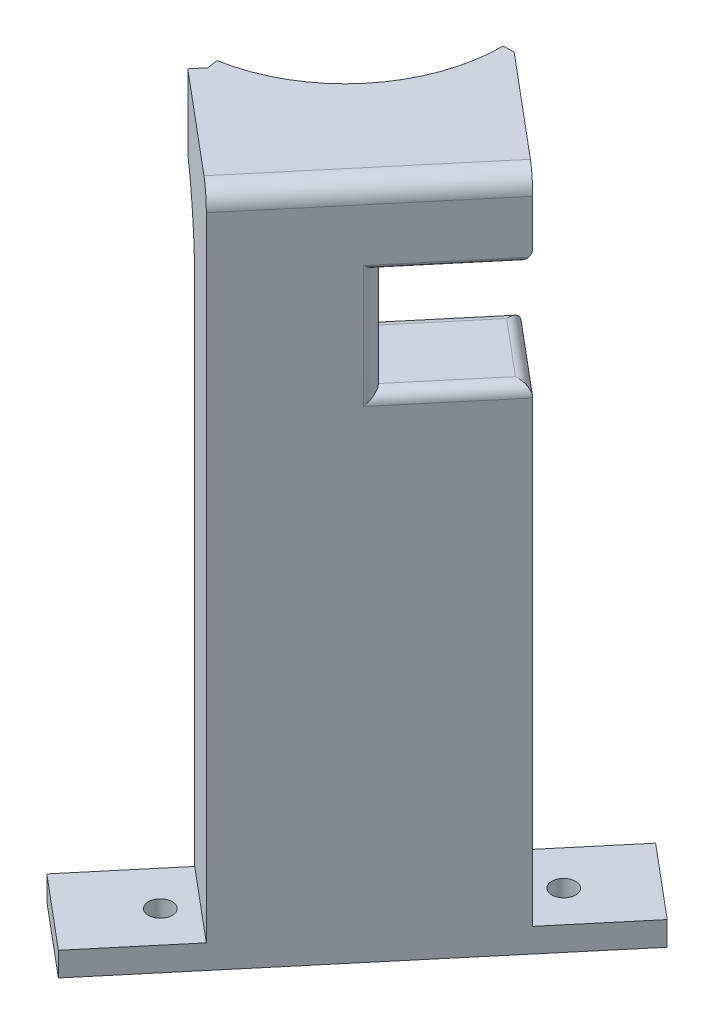
SolidWorks part; units mm, degrees
other "Markup1"
sketch "Sketch16" plane through (-5.2094, 14, 0) normal (0.4128, 0.8393, 0.3538) x (0.5563, 0.0753, -0.8276)
ref_plane "Front Plane" through (0, 0, 0) normal (0, 0, 1) x (1, 0, 0)
ref_plane "Top Plane" through (0, 0, 0) normal (0, 1, 0) x (1, 0, 0)
ref_plane "Right Plane" through (0, 0, 0) normal (1, 0, 0) x (0, 0, -1)
sketch "Sketch1" plane through (0, 0, 0) normal (0, 1, 0) x (1, 0, 0)
  line L0 (0, 0) -> (-45, 0)
  line L1 (0, 0) -> (-7.8142, 44.3163)
  circle A0 centre (0, 0) radius 42.1
  circle A1 centre (0, 0) radius 45
  circle A2 centre (0, 0) radius 30
  dimension "D1" = 84.2
  dimension "D2" = 90
  dimension "D3" = 60
  dimension "D4" = 80
extrude "Boss-Extrude1" add sketch "Sketch1" along normal blind 4 contours A2 L1 A0 L0 | L1 A1 L0 A0 region at (-25.6654, 0, -21.5358) region at (-43.55, 0, -0.5818)
extrude "Boss-Extrude2" add sketch "Sketch1<3>" along normal blind 14 contours L1 A1 L0 A0 region at (-43.55, 0, -0.5818)
sketch "Sketch1<3>" plane through (0, 0, 0) normal (0, 1, 0) x (1, 0, 0) same geometry as "Sketch1"
ref_plane "Plane1" through (0, -2.54, 0) normal (0, -1, 0) x (-1, 0, 0)
ref_plane "Plane2" through (0, -106.04, 0) normal (0, -1, 0) x (-1, 0, 0)
sketch "Sketch2" plane through (0, -106.04, 0) normal (0, -1, 0) x (-1, 0, 0)
  line L2 (7.8142, 44.3163) -> (5.2094, 29.5442)
  line L3 (30, 0) -> (45, 0)
  line L4 (7.8142, 44.3163) -> (5.2094, 29.5442)
  line L5 (30, 0) -> (45, 0)
  arc A2 (45, 0) -> (7.8142, 44.3163) centre (0, 0) ccw
  arc A3 (30, 0) -> (5.2094, 29.5442) centre (0, 0) ccw
  arc A4 (45, 0) -> (7.8142, 44.3163) centre (0, 0) ccw
  arc A5 (30, 0) -> (5.2094, 29.5442) centre (0, 0) ccw
  dimension "D1" = 0
sketch "Sketch3" plane through (0, 0, 0) normal (0, -1, 0) x (1, 0, 0)
  line L0 (-7.8142, -44.3163) -> (-45, 0)
  line L1 (-45, 0) -> (-75.6418, -25.7115)
  line L2 (-75.6418, -25.7115) -> (-38.4559, -70.0279)
  line L3 (-38.4559, -70.0279) -> (-7.8142, -44.3163)
  dimension "D1" = 40
extrude "Boss-Extrude3" add sketch "Sketch3" against normal up to surface (4 mm away) contours L3 L0 L1 L2 up to face at (-24.3855, 4, -20.4618)
sketch "Sketch4" plane through (0, 0, 0) normal (0, -1, 0) x (1, 0, 0)
  line L0 (-38.4559, -70.0279) -> (-19.3048, -53.9582)
  line L1 (-38.4559, -70.0279) -> (-7.8142, -44.3163) construction
  line L2 (-19.3048, -53.9582) -> (-56.4907, -9.6418)
  line L3 (-45, 0) -> (-75.6418, -25.7115) construction
  line L4 (-56.4907, -9.6418) -> (-75.6418, -25.7115)
  line L5 (-75.6418, -25.7115) -> (-38.4559, -70.0279)
  dimension "D1" = 25
extrude "Boss-Extrude4" add sketch "Sketch4" along normal blind 103.5
fillet "Fillet1" radius 20 1 edges at (-37.8978, 0, -31.8)
sketch "Sketch14" plane through (0, 4, 0) normal (0, 1, 0) x (1, 0, 0)
  line L0 (-7.8142, 44.3163) -> (-38.4559, 70.0279) construction
  line L1 (-38.4559, 70.0279) -> (-75.6418, 25.7115) construction
  line L2 (-75.6418, 25.7115) -> (-45, 0) construction
  line L9 (-7.3106, 41.4604) -> (-7.8142, 44.3163) construction
  line L10 (-45, 0) -> (-42.1, 0) construction
  line L12 (-7.8142, 44.3163) -> (-38.4559, 70.0279)
  line L13 (-38.4559, 70.0279) -> (-75.6418, 25.7115)
  line L14 (-75.6418, 25.7115) -> (-45, 0)
  line L15 (-7.3106, 41.4604) -> (-7.8142, 44.3163)
  line L16 (-45, 0) -> (-42.1, 0)
  arc A0 (-7.8142, 44.3163) -> (-45, 0) centre (0, 0) ccw construction
  arc A4 (-7.8142, 44.3163) -> (-45, 0) centre (0, 0) ccw construction
  arc A5 (-7.3106, 41.4604) -> (-42.1, 0) centre (0, 0) ccw construction
  arc A6 (-7.8142, 44.3163) -> (-45, 0) centre (0, 0) ccw
  arc A7 (-7.8142, 44.3163) -> (-45, 0) centre (0, 0) ccw
  arc A8 (-7.3106, 41.4604) -> (-42.1, 0) centre (0, 0) ccw
  arc M5 (-45, 0) -> (-7.8142, 44.3163) centre (0, 0) cw
  line M6 (-7.8142, 44.3163) -> (-38.4559, 70.0279)
  line M7 (-38.4559, 70.0279) -> (-75.6418, 25.7115)
  line M8 (-75.6418, 25.7115) -> (-45, 0)
extrude "Boss-Extrude7" add sketch "Sketch14" along normal blind 15 contours M8 M5 M6 M7 | A8 L15 L16 M5 region at (-44.3759, 4, -37.2358) region at (-8.1353, 4, -42.7874)
fillet "Fillet2" radius 5 1 edges at (-57.0489, 19, -47.8697)
sketch "Sketch6" plane through (18.5929, 0, -22.1582) normal (0.6428, 0, -0.766) x (-0.766, 0, -0.6428)
  line L0 (74.472, 14) -> (74.472, -103.5) construction
  line L1 (49.472, -103.5) -> (74.472, -103.5)
  line L2 (49.472, -103.5) -> (49.472, -97.5)
  line L3 (49.472, -97.5) -> (74.472, -97.5)
  line L4 (74.472, -103.5) -> (74.472, -97.5)
  dimension "D1" = 6
extrude "Boss-Extrude5" add sketch "Sketch6" along normal blind 25.4
sketch "Sketch7" plane through (-18.5929, 0, 22.1582) normal (-0.6428, 0, 0.766) x (0.766, 0, 0.6428)
  line L4 (-49.472, -103.5) -> (-49.472, -97.5)
  line L5 (-74.472, -103.5) -> (-49.472, -103.5)
  line L6 (-74.472, -97.5) -> (-74.472, -103.5)
  line L7 (-49.472, -97.5) -> (-74.472, -97.5)
  line L8 (-49.472, -103.5) -> (-49.472, -97.5)
  line L9 (-74.472, -103.5) -> (-49.472, -103.5)
  line L10 (-74.472, -97.5) -> (-74.472, -103.5)
  line L11 (-49.472, -97.5) -> (-74.472, -97.5)
  dimension "D1" = 0
extrude "Boss-Extrude6" add sketch "Sketch7" along normal blind 31.75
sketch "Sketch8" plane through (0, -97.5, 0) normal (0, 1, 0) x (1, 0, 0)
  circle A1 centre (-24.9091, 67.6646) radius 2.5527
  circle A2 centre (-24.9091, 67.6646) radius 2.5527
  circle A3 centre (-73.8895, 9.292) radius 2.5527
  circle A4 centre (-73.8895, 9.292) radius 2.5527
  dimension "D1" = 0
  dimension "D2" = 0
extrude "Cut-Extrude1" cut sketch "Sketch8" against normal blind 25.4 contours A4 | A2 region at (-73.8895, -97.5, -9.292)
sketch "Sketch9" plane through (0, -103.5, 0) normal (0, -1, 0) x (1, 0, 0)
  circle A0 centre (-73.8895, -9.292) radius 3.175
  circle A1 centre (-24.9091, -67.6646) radius 3.175
  dimension "D1" = 6.35
  dimension "D2" = 6.35
extrude "Cut-Extrude2" cut sketch "Sketch9" against normal blind 25.4
sketch "Sketch10" plane through (0, -97.5, 0) normal (0, 1, 0) x (1, 0, 0)
  line L1 (-76.8992, -14.6801) -> (-22.1291, -14.6801)
  line L2 (-76.8992, -14.6801) -> (-76.8992, 89.4854)
  line L3 (-76.8992, 89.4854) -> (-22.1291, 89.4854)
  line L4 (-22.1291, -14.6801) -> (-22.1291, 89.4854)
  line L5 (-144.4229, -81.7018) -> (69.164, -81.7018)
  line L6 (-144.4229, -81.7018) -> (-144.4229, 136.0266)
  line L7 (-144.4229, 136.0266) -> (69.164, 136.0266)
  line L8 (69.164, -81.7018) -> (69.164, 136.0266)
  line M11 (-75.6418, 25.7115) -> (-96.0503, 1.3896)
  line M12 (-96.0503, 1.3896) -> (-76.8992, -14.6801)
extrude "Cut-Extrude3" [suppressed] cut sketch "Sketch10" along normal blind 132.4 contours L5 L8 L7 L6 L4 L1 L2 L3 M12 M11 | L2 L1 L4 L3
ref_plane "Plane3" through (-64.7093, 0, -54.2976) normal (-0.766, 0, -0.6428) x (-0.6428, 0, 0.766)
sketch "Sketch18" plane through (0, -103.5, 0) normal (0, -1, 0) x (1, 0, 0)
  line L4 (-96.0503, -1.3896) -> (-22.1291, -89.4854)
  line L5 (-22.1291, -89.4854) -> (-2.978, -73.4157)
  line L6 (-2.978, -73.4157) -> (-76.8992, 14.6801)
  line L7 (-76.8992, 14.6801) -> (-96.0503, -1.3896)
  line L8 (-96.0503, -1.3896) -> (-22.1291, -89.4854)
  line L9 (-22.1291, -89.4854) -> (-2.978, -73.4157)
  line L10 (-2.978, -73.4157) -> (-76.8992, 14.6801)
  line L11 (-76.8992, 14.6801) -> (-96.0503, -1.3896)
  circle A1 centre (-24.9091, -67.6646) radius 3.175
  circle A2 centre (-24.9091, -67.6646) radius 3.175
  circle A3 centre (-73.8895, -9.292) radius 3.175
  circle A4 centre (-73.8895, -9.292) radius 3.175
  dimension "D1" = 0
  dimension "D2" = 0
  dimension "D3" = 0
extrude "Boss-Extrude9" add sketch "Sketch18" along normal blind 57.15
sketch "Sketch19" plane through (0, -97.5, 0) normal (0, 1, 0) x (1, 0, 0)
  line L0 (-56.4907, 9.6418) -> (-75.6418, 25.7115) construction
  line L1 (-75.6418, 25.7115) -> (-96.0503, 1.3896) construction
  line L2 (-96.0503, 1.3896) -> (-76.8992, -14.6801) construction
  line L3 (-76.8992, -14.6801) -> (-56.4907, 9.6418) construction
  line L4 (-38.4559, 70.0279) -> (-19.3048, 53.9582) construction
  line L5 (-19.3048, 53.9582) -> (-2.978, 73.4157) construction
  line L6 (-2.978, 73.4157) -> (-22.1291, 89.4854) construction
  line L7 (-22.1291, 89.4854) -> (-38.4559, 70.0279) construction
  line L8 (-56.4907, 9.6418) -> (-75.6418, 25.7115)
  line L9 (-75.6418, 25.7115) -> (-96.0503, 1.3896)
  line L10 (-96.0503, 1.3896) -> (-76.8992, -14.6801)
  line L11 (-76.8992, -14.6801) -> (-56.4907, 9.6418)
  line L12 (-38.4559, 70.0279) -> (-19.3048, 53.9582)
  line L13 (-19.3048, 53.9582) -> (-2.978, 73.4157)
  line L14 (-2.978, 73.4157) -> (-22.1291, 89.4854)
  line L15 (-22.1291, 89.4854) -> (-38.4559, 70.0279)
  circle A0 centre (-73.8895, 9.292) radius 3.175 construction
  circle A1 centre (-24.9091, 67.6646) radius 3.175 construction
  circle A2 centre (-73.8895, 9.292) radius 3.175
  circle A3 centre (-24.9091, 67.6646) radius 3.175
extrude "Cut-Extrude6" cut sketch "Sketch19" against normal blind 34.925
mirror "Mirror2" about plane through (-64.7093, 0, -54.2976) normal (-0.766, 0, -0.6428) of bodies 115 108
sketch "Sketch11" plane through (0, 19, 0) normal (0, 1, 0) x (1, 0, 0)
  line L0 (-67.6166, -74.3731) -> (52.0413, 76.7386)
  line L1 (52.0413, 76.7386) -> (-7.7876, 112.2458)
  line L2 (-7.7876, 112.2458) -> (-112.5342, -8.8462)
  line L3 (-112.5342, -8.8462) -> (-67.6166, -74.3731)
extrude "Cut-Extrude4" cut sketch "Sketch11" against normal through all both and the other way through all
sketch "Sketch13" plane through (-72.3698, 0, -60.7254) normal (0.766, 0, 0.6428) x (0.6428, 0, -0.766)
  line L0 (28.9254, 14) -> (28.9254, -132.425) construction
  line L1 (28.9254, -1) -> (0, -1)
  line L2 (28.9254, -1) -> (28.9254, -29.5)
  line L3 (28.9254, -29.5) -> (0, -29.5)
  line L4 (0, -1) -> (0, -29.5)
  line L6 (-28.9254, -103.5) -> (28.9254, -103.5)
  line L7 (-28.9254, 14) -> (-28.9254, -132.425) construction
  line L8 (28.9254, 14) -> (28.9254, -132.425) construction
  line L10 (-60.6754, -160.65) -> (54.3254, -160.65) construction
  line M11 (28.9254, -132.425) -> (28.9254, 14)
  dimension "D1" = 57.15
  dimension "D2" = 28.5
  dimension "D3" = 74
extrude "Cut-Extrude5" cut sketch "Sketch13" against normal blind 85 contours L1 L4 L3 M11 region at (-63.0733, -15.25, -71.8045)
fillet "Fillet3" radius 3 7 edges at (-94.0045, -9.0764, -78.8791) (-91.5209, -24.7465, -76.7951) (-82.2244, -29.5, -87.8742) (-63.3524, -29.5, -90.9185) (-63.0733, -29.5, -71.8045) (-72.3698, -15.25, -60.7254) (-68.6209, -1, -95.3392)
fillet "Fillet4" radius 1 1 edges at (-65.0017, -1, -69.5064) tangent propagation no
sketch "Sketch15" plane through (-18.5929, 0, 22.1582) normal (-0.6428, 0, 0.766) x (0.766, 0, 0.6428)
  line L5 (-119.472, -132.425) -> (-94.472, -132.425)
  line L6 (-94.472, -132.425) -> (-94.472, 14)
  line L7 (-99.472, 19) -> (-134.472, 19)
  line L8 (-134.472, 19) -> (-134.472, -0.6351)
  line L9 (-119.472, -20) -> (-119.472, -132.425)
  line L11 (-94.472, -132.425) -> (-94.472, 14)
  line L13 (-134.472, 19) -> (-134.472, -0.6351)
  line L14 (-119.472, -20) -> (-119.472, -132.425)
  line L16 (-99.472, 19) -> (-134.472, 19)
  line L18 (-119.472, -132.425) -> (-94.472, -132.425)
  arc A2 (-94.472, 14) -> (-99.472, 19) centre (-99.472, 14) ccw
  arc A3 (-119.472, -20) -> (-134.472, -0.6351) centre (-139.472, -20) ccw
  arc A5 (-119.472, -20) -> (-134.472, -0.6351) centre (-139.472, -20) ccw
  arc A6 (-94.472, 14) -> (-99.472, 19) centre (-99.472, 14) ccw
  dimension "D1" = 0
extrude "Boss-Extrude8" add sketch "Sketch15" along normal blind 3.81
sketch "Sketch20" plane through (0, -132.425, 0) normal (0, 1, 0) x (1, 0, 0)
  line L4 (-53.7768, 82.8836) -> (-37.45, 102.3411)
  line L5 (-37.45, 102.3411) -> (-56.6011, 118.4108)
  line L6 (-56.6011, 118.4108) -> (-72.9279, 98.9533)
  line L7 (-72.9279, 98.9533) -> (-53.7768, 82.8836)
  line L8 (-53.7768, 82.8836) -> (-37.45, 102.3411)
  line L9 (-37.45, 102.3411) -> (-56.6011, 118.4108)
  line L10 (-56.6011, 118.4108) -> (-72.9279, 98.9533)
  line L11 (-72.9279, 98.9533) -> (-53.7768, 82.8836)
  line L12 (-93.4117, 35.6486) -> (-112.5628, 51.7183)
  line L13 (-112.5628, 51.7183) -> (-130.5223, 30.315)
  line L14 (-130.5223, 30.315) -> (-111.3712, 14.2453)
  line L15 (-111.3712, 14.2453) -> (-93.4117, 35.6486)
  line L16 (-93.4117, 35.6486) -> (-112.5628, 51.7183)
  line L17 (-112.5628, 51.7183) -> (-130.5223, 30.315)
  line L18 (-130.5223, 30.315) -> (-111.3712, 14.2453)
  line L19 (-111.3712, 14.2453) -> (-93.4117, 35.6486)
  circle A0 centre (-107.437, 37.4417) radius 3.175 construction
  circle A1 centre (-107.437, 37.4417) radius 3.175
  circle A2 centre (-58.4566, 95.8143) radius 3.175 construction
  circle A3 centre (-58.4566, 95.8143) radius 3.175
  dimension "D1" = 0
  dimension "D2" = 0
extrude "Cut-Extrude7" cut sketch "Sketch20" against normal blind 21.844
